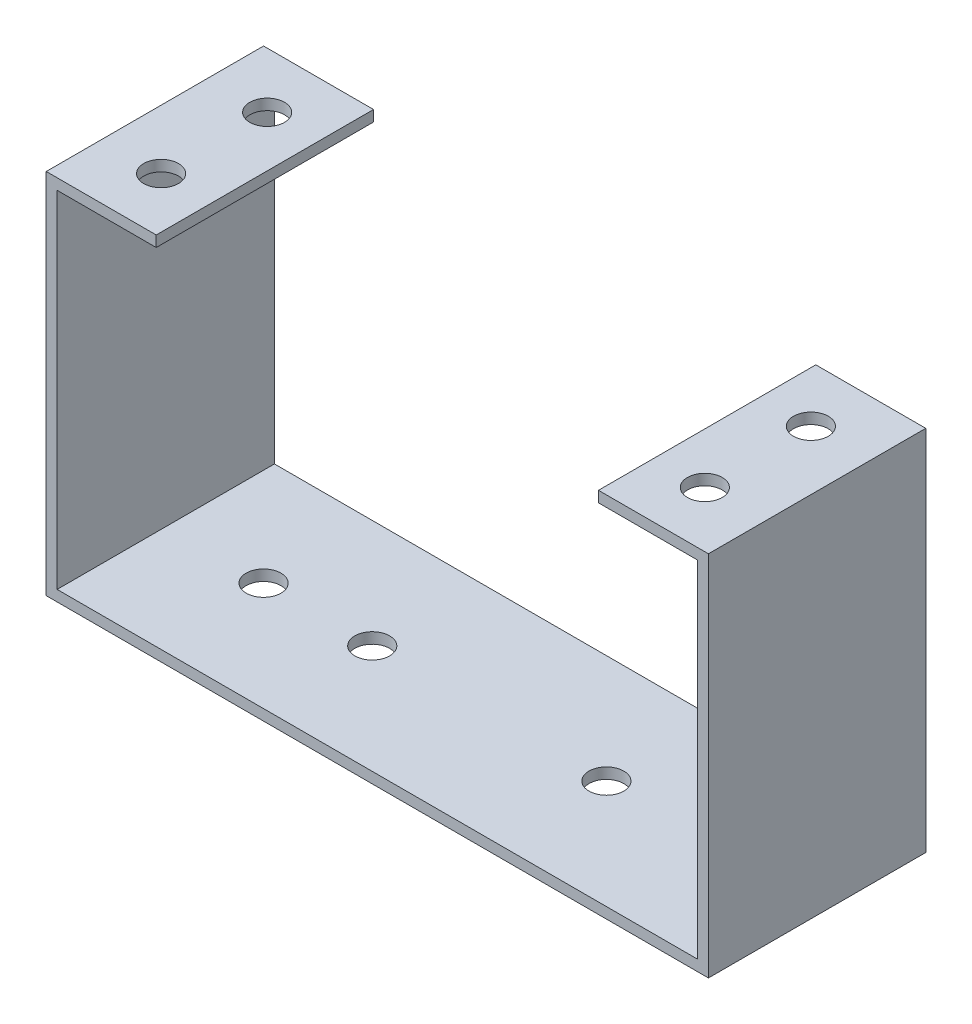
SolidWorks part; units mm, degrees
ref_plane "正面" through (0, 0, 0) normal (0, 0, 1) x (1, 0, 0)
ref_plane "平面" through (0, 0, 0) normal (0, 1, 0) x (1, 0, 0)
ref_plane "右側面" through (0, 0, 0) normal (1, 0, 0) x (0, 0, -1)
sketch "ｽｹｯﾁ2" plane through (0, 0, 0) normal (0, 1, 0) x (1, 0, 0)
  line L1 (0, 0) -> (60.94, 0)
  line L2 (0, 0) -> (0, 20)
  line L3 (0, 20) -> (60.94, 20)
  line L4 (60.94, 0) -> (60.94, 20)
extrude "ﾎﾞｽ - 押し出し1" add sketch "ｽｹｯﾁ2" along normal blind 1
sketch "ｽｹｯﾁ3" plane through (0, 1, 0) normal (0, 1, 0) x (1, 0, 0)
  line L0 (0, 0) -> (60.94, 0) construction
  line L1 (60.94, 20) -> (59.94, 20)
  line L2 (60.94, 20) -> (60.94, 0)
  line L3 (60.94, 0) -> (59.94, 0)
  line L4 (59.94, 20) -> (59.94, 0)
extrude "ﾎﾞｽ - 押し出し2" add sketch "ｽｹｯﾁ3" along normal blind 32.81
sketch "ｽｹｯﾁ4" plane through (0, 1, 0) normal (0, 1, 0) x (1, 0, 0)
  line L0 (0, 0) -> (59.94, 0) construction
  line L1 (0, 20) -> (1, 20)
  line L2 (0, 20) -> (0, 0)
  line L3 (0, 0) -> (1, 0)
  line L4 (1, 20) -> (1, 0)
extrude "ﾎﾞｽ - 押し出し3" add sketch "ｽｹｯﾁ4" along normal blind 32.81
sketch "ｽｹｯﾁ9" plane through (59.94, 0, 0) normal (-1, 0, 0) x (0, 0, 1)
  line L0 (0, 33.81) -> (0, 1) construction
  line L1 (-20, 33.81) -> (0, 33.81)
  line L2 (-20, 33.81) -> (-20, 32.81)
  line L3 (-20, 32.81) -> (0, 32.81)
  line L4 (0, 33.81) -> (0, 32.81)
extrude "ﾎﾞｽ - 押し出し8" add sketch "ｽｹｯﾁ9" along normal blind 9.12
sketch "ｽｹｯﾁ10" plane through (1, 0, 0) normal (1, 0, 0) x (0, 0, -1)
  line L0 (20, 33.81) -> (20, 1) construction
  line L1 (0, 33.81) -> (20, 33.81)
  line L2 (0, 33.81) -> (0, 32.81)
  line L3 (0, 32.81) -> (20, 32.81)
  line L4 (20, 33.81) -> (20, 32.81)
extrude "ﾎﾞｽ - 押し出し9" add sketch "ｽｹｯﾁ10" along normal blind 9.12
sketch "ｽｹｯﾁ13" plane through (0, 33.81, 0) normal (0, 1, 0) x (1, 0, 0)
  circle A0 centre (55.49, 5.12) radius 1.6
extrude "ｶｯﾄ - 押し出し2" cut sketch "ｽｹｯﾁ13" against normal blind 1
sketch "ｽｹｯﾁ14" plane through (0, 33.81, 0) normal (0, 1, 0) x (1, 0, 0)
  circle A0 centre (55.49, 14.88) radius 1.6
extrude "ｶｯﾄ - 押し出し3" cut sketch "ｽｹｯﾁ14" against normal blind 1
sketch "ｽｹｯﾁ15" plane through (0, 33.81, 0) normal (0, 1, 0) x (1, 0, 0)
  circle A0 centre (5.45, 5.12) radius 1.6
extrude "ｶｯﾄ - 押し出し4" cut sketch "ｽｹｯﾁ15" against normal blind 1
sketch "ｽｹｯﾁ16" plane through (0, 33.81, 0) normal (0, 1, 0) x (1, 0, 0)
  circle A0 centre (5.45, 14.88) radius 1.6
extrude "ｶｯﾄ - 押し出し5" cut sketch "ｽｹｯﾁ16" against normal blind 1
sketch "ｽｹｯﾁ17" plane through (0, 0, 0) normal (0, -1, 0) x (-1, 0, 0)
  circle A0 centre (-41.55, 10) radius 1.6
extrude "ｶｯﾄ - 押し出し6" cut sketch "ｽｹｯﾁ17" against normal blind 1 contours A0
sketch "ｽｹｯﾁ18" plane through (0, 0, 0) normal (0, -1, 0) x (-1, 0, 0)
  circle A0 centre (-10, 10) radius 1.6
extrude "ｶｯﾄ - 押し出し7" cut sketch "ｽｹｯﾁ18" against normal blind 1
sketch "ｽｹｯﾁ19" plane through (0, 0, 0) normal (0, -1, 0) x (-1, 0, 0)
  circle A0 centre (-20, 10) radius 1.6
extrude "ｶｯﾄ - 押し出し8" cut sketch "ｽｹｯﾁ19" against normal blind 1
